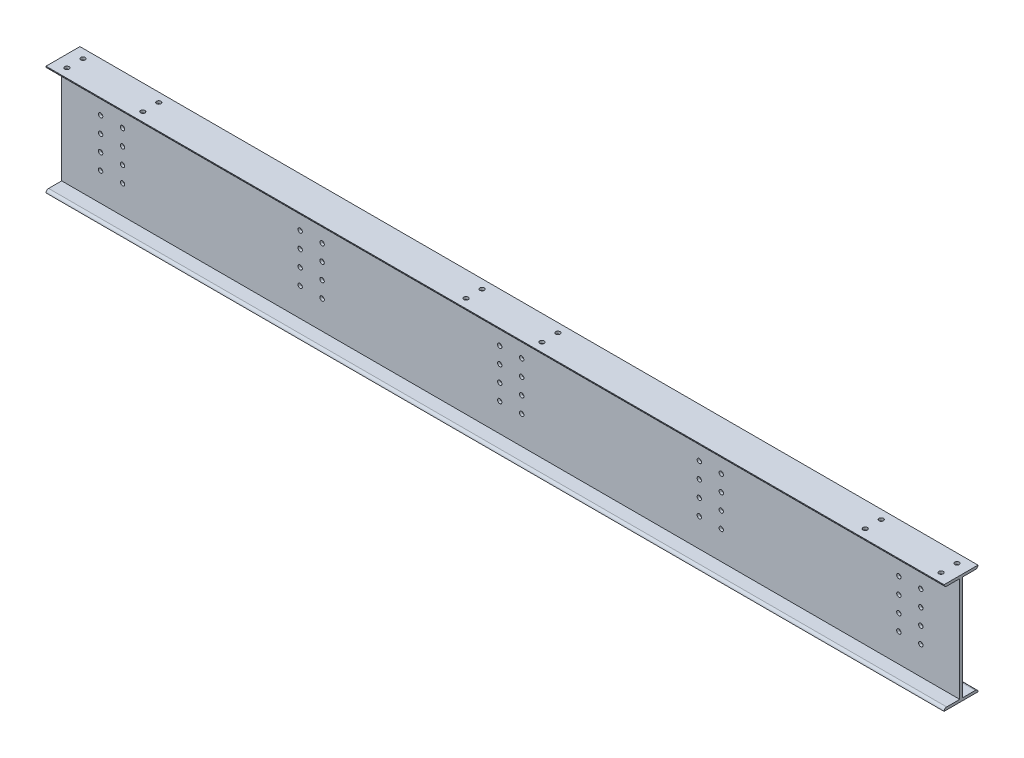
SolidWorks part; units mm, degrees
ref_plane "前视基准面" through (0, 0, 0) normal (0, 0, 1) x (1, 0, 0)
ref_plane "上视基准面" through (0, 0, 0) normal (0, 1, 0) x (1, 0, 0)
ref_plane "右视基准面" through (0, 0, 0) normal (1, 0, 0) x (0, 0, -1)
sketch "草图1" plane through (0, 0, 0) normal (0, 0, 1) x (1, 0, 0)
  line L1 (0, 550) -> (4500, 550)
  line L2 (0, 550) -> (0, 0)
  line L3 (0, 0) -> (4500, 0)
  line L4 (4500, 550) -> (4500, 0)
  dimension "D1" = 4500
  dimension "D2" = 550
extrude "拉伸1" add sketch "草图1" along normal blind 170
sketch "草图2" plane through (0, 0, 170) normal (0, 0, 1) x (1, 0, 0)
  line L0 (0, 0) -> (4500, 0) construction
  line L1 (0, 550) -> (0, 0) construction
  circle A0 centre (195, 155) radius 11
  dimension "D1" = 155
  dimension "D2" = 195
extrude "切除-拉伸1" cut sketch "草图2" against normal through all
pattern_linear "阵列(线性)1" count 2 spacing 110 along (1, 0, 0) count 4 spacing 80 along (0, 1, 0) of "切除-拉伸1"
pattern_linear "阵列(线性)2" count 5 spacing 1000 along (1, 0, 0) of "阵列(线性)1", "切除-拉伸1"
sketch "草图4" plane through (0, 550, 0) normal (0, 1, 0) x (1, 0, 0)
  line L0 (0, -170) -> (0, 0) construction
  circle A0 centre (60, -125) radius 11
  circle A1 centre (60, -45) radius 11
  point P2 (0, -85)
  dimension "D1" = 40
  dimension "D3" = 60
  dimension "D2" = 60
  dimension "D4" = 80
extrude "切除-拉伸2" cut sketch "草图4" against normal blind 200
pattern_linear "阵列(线性)3" count 2 spacing 380 along (1, 0, 0) of "切除-拉伸2"
pattern_linear "阵列(线性)4" count 3 spacing 2000 along (1, 0, 0) of "阵列(线性)3", "切除-拉伸2"
sketch "草图7" plane through (0, 0, 0) normal (-1, 0, 0) x (0, 0, 1)
  line L0 (170, 550) -> (170, 0) construction
  line L1 (91.5, 537) -> (170, 537)
  line L2 (91.5, 537) -> (91.5, 13)
  line L3 (91.5, 13) -> (170, 13)
  line L4 (170, 537) -> (170, 13)
  line L5 (170, 550) -> (0, 550) construction
  line L6 (170, 550) -> (0, 550) construction
  line L7 (0, 550) -> (0, 0) construction
  line L8 (0, 537) -> (78.5, 537)
  line L9 (0, 537) -> (0, 13)
  line L10 (0, 13) -> (78.5, 13)
  line L11 (78.5, 537) -> (78.5, 13)
  line L12 (170, 0) -> (0, 0) construction
  point P16 (85, 550)
  dimension "D1" = 6.5
  dimension "D2" = 13
  dimension "D3" = 13
extrude "切除-拉伸3" cut sketch "草图7" against normal through all
fillet "圆角1" radius 13 1 edges at (2250, 537, 0)
fillet "圆角2" radius 13 1 edges at (2250, 537, 170)
fillet "圆角3" radius 13 1 edges at (2250, 13, 0)
fillet "圆角4" radius 13 1 edges at (2250, 13, 170)
